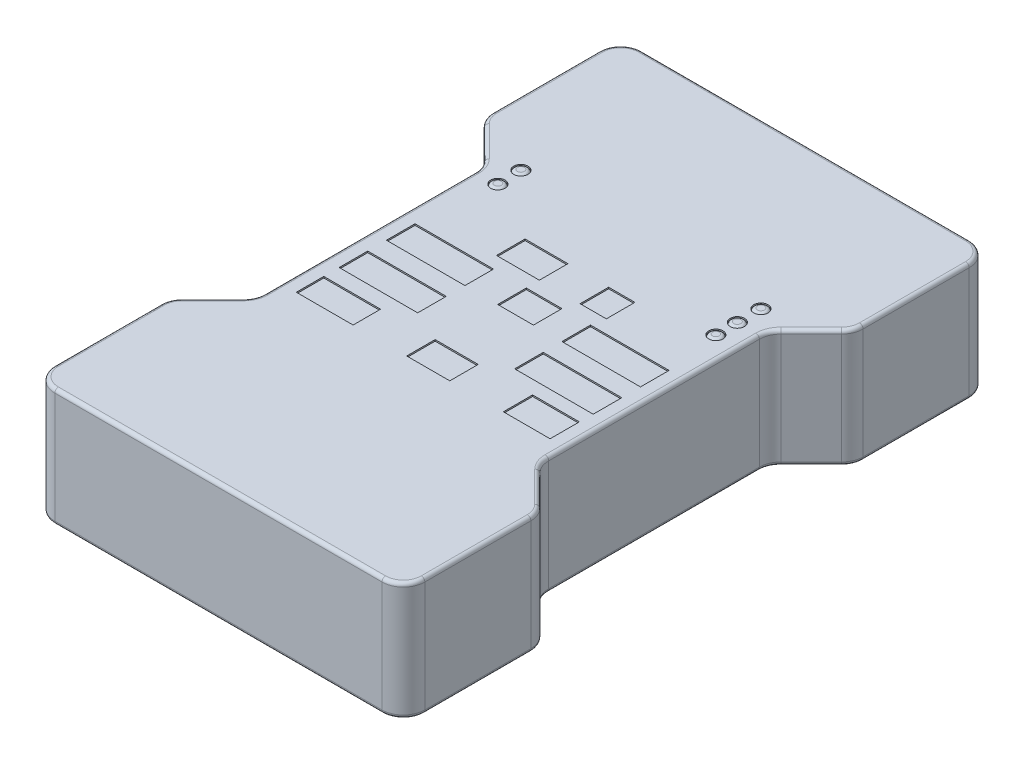
SolidWorks part; units mm, degrees
ref_plane "Ön Düzlem" through (0, 0, 0) normal (0, 0, 1) x (1, 0, 0)
ref_plane "Üst Düzlem" through (0, 0, 0) normal (0, 1, 0) x (1, 0, 0)
ref_plane "Sağ Düzlem" through (0, 0, 0) normal (1, 0, 0) x (0, 0, -1)
sketch "Çizim2" plane through (0, 0, 0) normal (0, 1, 0) x (1, 0, 0)
  line L0 (-30.4945, -25.4052) -> (15.3055, -25.4052)
  line L1 (-33.4945, -22.4052) -> (-33.4945, -7.5579)
  line L2 (-33.4945, -6.3052) -> (-33.4845, -6.3052)
  line L3 (-27.4745, 0.9474) -> (-27.4745, 30.4421)
  line L4 (-33.4845, 37.6948) -> (-33.4945, 37.6948)
  line L5 (-33.4945, 38.9474) -> (-33.4945, 53.7948)
  line L6 (-30.4945, 56.7948) -> (15.3055, 56.7948)
  line L7 (18.3055, 53.7948) -> (18.3055, 38.9474)
  line L8 (18.3055, 37.6948) -> (18.2955, 37.6948)
  line L9 (12.2855, 30.4421) -> (12.2855, 0.9474)
  line L10 (18.2955, -6.3052) -> (18.3055, -6.3052)
  line L11 (18.3055, -7.5579) -> (18.3055, -22.4052)
  line L12 (-32.6159, -5.4365) -> (-28.3532, -1.1739)
  line L13 (-28.3532, 32.5635) -> (-32.6159, 36.8261)
  line L14 (17.4268, 36.8261) -> (13.1641, 32.5635)
  line L15 (13.1641, -1.1739) -> (17.4268, -5.4365)
  arc A0 (-30.4945, -25.4052) -> (-33.4945, -22.4052) centre (-30.4945, -22.4052) cw
  arc A1 (15.3055, -25.4052) -> (18.3055, -22.4052) centre (15.3055, -22.4052) ccw
  arc A2 (18.3055, 53.7948) -> (15.3055, 56.7948) centre (15.3055, 53.7948) ccw
  arc A3 (-30.4945, 56.7948) -> (-33.4945, 53.7948) centre (-30.4945, 53.7948) ccw
  arc A4 (17.4268, 36.8261) -> (18.3055, 38.9474) centre (15.3055, 38.9474) ccw
  arc A5 (12.2855, 30.4421) -> (13.1641, 32.5635) centre (15.2855, 30.4421) cw
  arc A6 (13.1641, -1.1739) -> (12.2855, 0.9474) centre (15.2855, 0.9474) cw
  arc A7 (18.3055, -7.5579) -> (17.4268, -5.4365) centre (15.3055, -7.5579) ccw
  arc A8 (-32.6159, -5.4365) -> (-33.4945, -7.5579) centre (-30.4945, -7.5579) ccw
  arc A9 (-27.4745, 0.9474) -> (-28.3532, -1.1739) centre (-30.4745, 0.9474) cw
  arc A10 (-27.4745, 30.4421) -> (-28.3532, 32.5635) centre (-30.4745, 30.4421) ccw
  arc A11 (-33.4945, 38.9474) -> (-32.6159, 36.8261) centre (-30.4945, 38.9474) ccw
  point P2 (12.2855, 37.6948)
  point P4 (-27.4745, -6.3052)
  point P5 (-27.4745, 37.6948)
  point P11 (12.2855, -6.3052)
extrude "Yükseklik-Ekstrüzyon1" add sketch "Çizim2" along normal blind 16.5 contours L5 A11 L13 A10 L3 A9 L12 A8 L1 A0 L0 A1 L11 A7 L15 A6 L9 A5 L14 A4 L7 A2 L6 A3 region at (-7.5945, 0, -15.6948)
fillet "Radyus1" radius 0.5 48 edges at (18.0771, 0, 6.4098) (15.2955, 0, 3.3052) (12.5138, 0, 0.2006) (12.2855, 0, -15.6948) (12.5138, 0, -31.5902) (15.2955, 0, -34.6948) (18.0771, 0, -37.7994) (18.3055, 0, -46.3711) (17.4268, 0, -55.9161) (-7.5945, 0, -56.7948) (-32.6159, 0, -55.9161) (-33.4945, 0, -46.3711) (-33.2662, 0, -37.7994) (-30.4845, 0, -34.6948) (-27.7029, 0, -31.5902) (-27.4745, 0, -15.6948) (-27.7029, 0, 0.2006) (-30.4845, 0, 3.3052) (-33.2662, 0, 6.4098) (-33.4945, 0, 14.9815) (-32.6159, 0, 24.5265) (-7.5945, 0, 25.4052) (17.4268, 0, 24.5265) (18.3055, 0, 14.9815) (-32.6159, 16.5, -55.9161) (-7.5945, 16.5, -56.7948) (17.4268, 16.5, -55.9161) (18.3055, 16.5, -46.3711) (18.0771, 16.5, -37.7994) (15.2955, 16.5, -34.6948) (12.5138, 16.5, -31.5902) (12.2855, 16.5, -15.6948) (12.5138, 16.5, 0.2006) (15.2955, 16.5, 3.3052) (18.0771, 16.5, 6.4098) (18.3055, 16.5, 14.9815) (17.4268, 16.5, 24.5265) (-7.5945, 16.5, 25.4052) (-32.6159, 16.5, 24.5265) (-33.4945, 16.5, 14.9815) (-33.2662, 16.5, 6.4098) (-30.4845, 16.5, 3.3052) (-27.7029, 16.5, 0.2006) (-27.4745, 16.5, -15.6948) (-27.7029, 16.5, -31.5902) (-30.4845, 16.5, -34.6948) (-33.2662, 16.5, -37.7994) (-33.4945, 16.5, -46.3711)
sketch "Çizim4" plane through (0, 16.5, 0) normal (0, 1, 0) x (1, 0, 0)
  line L8 (-15.774, 25.7039) -> (-9.774, 25.7039)
  line L10 (-25.3222, 7.0752) -> (-25.3222, 3.2298)
  line L11 (-25.3222, 3.2298) -> (-17.3716, 3.2298)
  line L12 (-17.3716, 3.2298) -> (-17.3716, 7.0752)
  line L13 (-17.3716, 7.0752) -> (-25.3222, 7.0752)
  line L14 (3.6601, 7.3249) -> (3.6601, 3.2298)
  line L15 (3.6601, 3.2298) -> (10.2055, 3.2298)
  line L17 (10.2055, 7.3249) -> (3.6601, 7.3249)
  line L18 (-9.8716, 7.2108) -> (-9.8716, 3.2298)
  line L19 (-9.8716, 3.2298) -> (-3.8399, 3.2298)
  line L20 (-3.8399, 3.2298) -> (-3.8399, 7.2108)
  line L21 (-3.8399, 7.2108) -> (-9.8716, 7.2108)
  line L24 (10.2055, 3.2298) -> (10.2055, 7.3249)
  line L25 (-15.774, 25.7039) -> (-15.774, 21.7039)
  line L26 (-25.3222, 13.2258) -> (-14.3281, 13.2258)
  line L27 (-25.3222, 13.2258) -> (-25.3222, 9.2258)
  line L28 (-25.3222, 9.2258) -> (-14.3281, 9.2258)
  line L29 (-14.3281, 13.2258) -> (-14.3281, 9.2258)
  line L30 (10.2445, 13.2258) -> (-0.7555, 13.2258)
  line L31 (10.2445, 13.2258) -> (10.2445, 9.2258)
  line L32 (10.2445, 9.2258) -> (-0.7555, 9.2258)
  line L33 (-0.7555, 13.2258) -> (-0.7555, 9.2258)
  line L34 (-25.3222, 19.843) -> (-14.3276, 19.843)
  line L35 (-25.3222, 19.843) -> (-25.3222, 15.843)
  line L36 (-25.3222, 15.843) -> (-14.3276, 15.843)
  line L37 (-14.3276, 19.843) -> (-14.3276, 15.843)
  line L38 (10.2445, 19.843) -> (-0.7555, 19.843)
  line L39 (10.2445, 19.843) -> (10.2445, 15.843)
  line L40 (10.2445, 15.843) -> (-0.7555, 15.843)
  line L41 (-0.7555, 19.843) -> (-0.7555, 15.843)
  line L42 (-9.743, 19.843) -> (-4.743, 19.843)
  line L43 (-9.743, 19.843) -> (-9.743, 15.843)
  line L44 (-9.743, 15.843) -> (-4.743, 15.843)
  line L45 (-4.743, 19.843) -> (-4.743, 15.843)
  line L46 (-15.774, 21.7039) -> (-9.774, 21.7039)
  line L47 (-9.774, 25.7039) -> (-9.774, 21.7039)
  line L48 (-4.0723, 25.7039) -> (-0.3968, 25.7039)
  line L49 (-4.0723, 25.7039) -> (-4.0723, 21.7039)
  line L50 (-4.0723, 21.7039) -> (-0.3968, 21.7039)
  line L51 (-0.3968, 25.7039) -> (-0.3968, 21.7039)
  circle A0 centre (9.2108, 30.4421) radius 1
  circle A1 centre (9.2055, 33.7399) radius 1
  circle A2 centre (9.2108, 27.4308) radius 0.9947
  circle A3 centre (-24.3958, 33.7399) radius 1
  circle A4 centre (-24.3222, 30.4421) radius 1
  point P0 (0, 0)
extrude "Kes-Ekstrüzyon2" cut sketch "Çizim4" against normal blind 0.2
sketch "Çizim5" plane through (0, 16.5, 0) normal (0, 1, 0) x (1, 0, 0)
  circle A0 centre (9.2055, 33.7399) radius 0.949
sketch "Çizim7" plane through (0, 16.3, 0) normal (0, 1, 0) x (1, 0, 0)
  circle A0 centre (9.2108, 30.4421) radius 0.9454
extrude "Yükseklik-Ekstrüzyon6" add sketch "Çizim7" along normal blind 0.3
fillet "Radyus6" radius 0.5 1 edges at (9.2108, 16.6, -29.4968)
sketch "Çizim8" plane through (0, 16.3, 0) normal (0, 1, 0) x (1, 0, 0)
  circle A0 centre (9.2108, 27.4308) radius 0.9204
extrude "Yükseklik-Ekstrüzyon8" add sketch "Çizim8" along normal blind 0.3
fillet "Radyus7" radius 0.5 1 edges at (9.2108, 16.6, -26.5104)
sketch "Çizim9" plane through (0, 16.3, 0) normal (0, 1, 0) x (1, 0, 0)
  circle A1 centre (-24.3222, 30.4421) radius 0.9459
extrude "Yükseklik-Ekstrüzyon9" add sketch "Çizim9" along normal blind 0.3
fillet "Radyus8" radius 0.5 1 edges at (-24.3222, 16.6, -29.4962)
sketch "Çizim10" plane through (0, 16.3, 0) normal (0, 1, 0) x (1, 0, 0)
  circle A0 centre (-24.3958, 33.7399) radius 0.9491
extrude "Yükseklik-Ekstrüzyon10" add sketch "Çizim10" along normal blind 0.3
fillet "Radyus9" radius 0.5 1 edges at (-24.3958, 16.6, -32.7908)
sketch "Çizim11" plane through (0, 16.3, 0) normal (0, 1, 0) x (1, 0, 0)
  circle A0 centre (9.2055, 33.7399) radius 0.9495
extrude "Yükseklik-Ekstrüzyon11" add sketch "Çizim11" along normal blind 0.3
fillet "Radyus10" radius 0.5 1 edges at (9.2055, 16.6, -32.7904)
